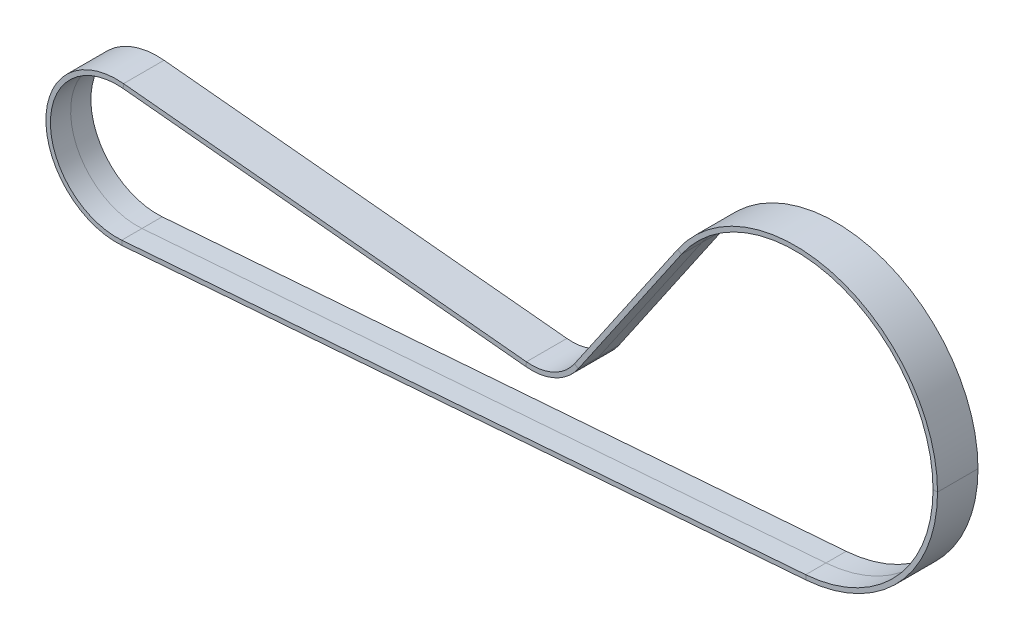
SolidWorks part; units mm, degrees
ref_plane "Front Plane" through (0, 0, 0) normal (0, 0, 1) x (1, 0, 0)
ref_plane "Top Plane" through (0, 0, 0) normal (0, 1, 0) x (1, 0, 0)
ref_plane "Right Plane" through (0, 0, 0) normal (1, 0, 0) x (0, 0, -1)
sketch "Sketch2" plane through (0, 0, 0) normal (0, 0, 1) x (1, 0, 0)
  line L0 (0, 0) -> (1, 0) construction
  line L1 (0, 0) -> (0, 1) construction
  line L2 (4.0693, -32.1661) -> (-148.0309, -43.7974)
  line L3 (-147.6828, -11.233) -> (-58.102, -20.0134)
  line L4 (-47.953, -15.2808) -> (-25.0079, 18.2268)
  arc A0 (-25.0079, 18.2268) -> (4.0693, -32.1661) centre (1.6096, 0) cw
  arc A1 (-148.0309, -43.7974) -> (-147.6828, -11.233) centre (-149.2772, -27.5) cw
  arc A2 (-58.102, -20.0134) -> (-47.953, -15.2808) centre (-57.029, -9.0658) ccw
sketch "Sketch3" plane through (0, 0, 0) normal (0, 1, 0) x (1, 0, 0)
  line L0 (32.26, 0) -> (32.26, -4.5)
  line L1 (-25.0079, 0) -> (33.8696, 0) construction
  line L2 (32.26, -4.5) -> (33.26, -4.5)
  line L3 (33.26, -4.5) -> (33.26, 4.5)
  line L4 (33.26, 4.5) -> (32.26, 4.5)
  line L5 (32.26, 4.5) -> (32.26, 0)
  point P8 (33.26, 0)
  dimension "D1" = 1
  dimension "D2" = 9
  dimension "D3" = 32.26
sweep "Sweep1" add profiles "Sketch3" path "Sketch2"
